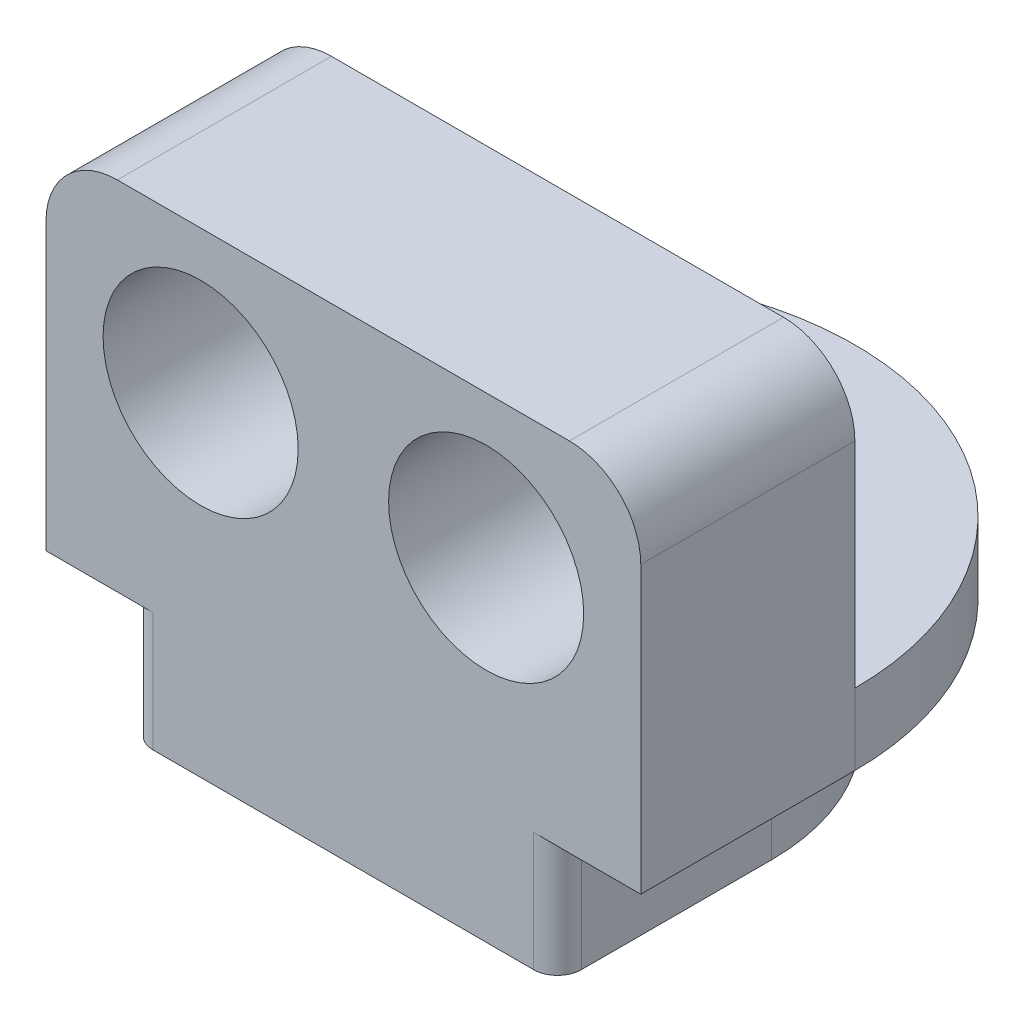
SolidWorks part; units mm, degrees
ref_plane "正面" through (0, 0, 0) normal (0, 0, 1) x (1, 0, 0)
ref_plane "平面" through (0, 0, 0) normal (0, 1, 0) x (1, 0, 0)
ref_plane "右側面" through (0, 0, 0) normal (1, 0, 0) x (0, 0, -1)
sketch "ｽｹｯﾁ1" plane through (0, 0, 0) normal (0, 1, 0) x (1, 0, 0)
  line L0 (-9, 0) -> (-9, -9)
  line L1 (-9, -9) -> (9, -9)
  line L2 (9, -9) -> (9, 0)
  arc A0 (9, 0) -> (-9, 0) centre (0, 0) ccw
  circle A1 centre (0, 0) radius 7.6
  dimension "D1" = 15.2
  dimension "D2" = 18
extrude "ﾎﾞｽ - 押し出し1" add sketch "ｽｹｯﾁ1" along normal blind 5
sketch "ｽｹｯﾁ2" plane through (0, 5, 0) normal (0, 1, 0) x (1, 0, 0)
  line L0 (9, -9) -> (9, 0) construction
  line L1 (-9, -9) -> (9, -9)
  line L2 (-9, -9) -> (-9, -4)
  line L3 (-9, -4) -> (9, -4)
  line L4 (9, -9) -> (9, -4)
  dimension "D1" = 5
extrude "ﾎﾞｽ - 押し出し2" add sketch "ｽｹｯﾁ2" along normal blind 15
sketch "ｽｹｯﾁ4" plane through (0, 5, 0) normal (0, 1, 0) x (1, 0, 0)
  line L2 (-12.5, 0) -> (-12.5, -9)
  line L3 (-12.5, -9) -> (12.5, -9)
  line L4 (12.5, -9) -> (12.5, 0)
  line L5 (-9, -9) -> (9, -9) construction
  arc A0 (12.5, 0) -> (-12.5, 0) centre (0, 0) ccw
  dimension "D1" = 25
extrude "ﾎﾞｽ - 押し出し3" add sketch "ｽｹｯﾁ4" along normal blind 3
sketch "ｽｹｯﾁ5" plane through (0, 8, 0) normal (0, 1, 0) x (1, 0, 0)
  line L1 (-9, -4) -> (-12.5, -4)
  line L2 (-9, -4) -> (-9, -9)
  line L3 (-9, -9) -> (-12.5, -9)
  line L4 (-12.5, -4) -> (-12.5, -9)
  line L5 (9, -4) -> (12.5, -4)
  line L6 (9, -4) -> (9, -9)
  line L7 (9, -9) -> (12.5, -9)
  line L8 (12.5, -4) -> (12.5, -9)
extrude "ﾎﾞｽ - 押し出し4" add sketch "ｽｹｯﾁ5" along normal up to surface (12 mm away) up to face at (0, 20, 6.5)
sketch "ｽｹｯﾁ3" plane through (0, 0, 9) normal (0, 0, 1) x (1, 0, 0)
  line L0 (-9, 14) -> (9, 14) construction
  line L3 (0, 20) -> (0, 5) construction
  line L4 (-12.5, 20) -> (12.5, 20) construction
  line L5 (-9, 5) -> (9, 5) construction
  line L6 (-9, 5) -> (-9, 0) construction
  line L7 (9, 5) -> (9, 0) construction
  line L8 (-12.5, 20) -> (12.5, 20) construction
  circle A0 centre (-6, 14) radius 4.1
  circle A1 centre (6, 14) radius 4.1
  dimension "D1" = 8.2
  dimension "D2" = 12
  dimension "D3" = 6
extrude "ｶｯﾄ - 押し出し1" cut sketch "ｽｹｯﾁ3" against normal through all
fillet "ﾌｨﾚｯﾄ4" radius 1 2 edges at (-9, 2.5, 9) (9, 2.5, 9)
sketch "ｽｹｯﾁ6" plane through (0, 0, 4) normal (0, 0, -1) x (-1, 0, 0)
  line L4 (12.5, 20) -> (-12.5, 20)
  line L5 (-12.5, 20) -> (-12.5, 8)
  line L6 (-12.5, 8) -> (12.5, 8)
  line L7 (12.5, 8) -> (12.5, 20)
  line L8 (12.5, 20) -> (-12.5, 20)
  line L9 (-12.5, 20) -> (-12.5, 8)
  line L10 (-12.5, 8) -> (12.5, 8)
  line L11 (12.5, 8) -> (12.5, 20)
  circle A1 centre (-6, 14) radius 4.1
  circle A2 centre (-6, 14) radius 4.1
  circle A3 centre (6, 14) radius 4.1
  circle A4 centre (6, 14) radius 4.1
  dimension "D1" = 0
  dimension "D2" = 0
  dimension "D3" = 0
extrude "ﾎﾞｽ - 押し出し5" add sketch "ｽｹｯﾁ6" along normal up to vertex (4 mm away) up to point (12.5, 8, 0)
fillet "ﾌｨﾚｯﾄ5" radius 3 2 edges at (12.5, 20, 4.5) (-12.5, 20, 4.5)
